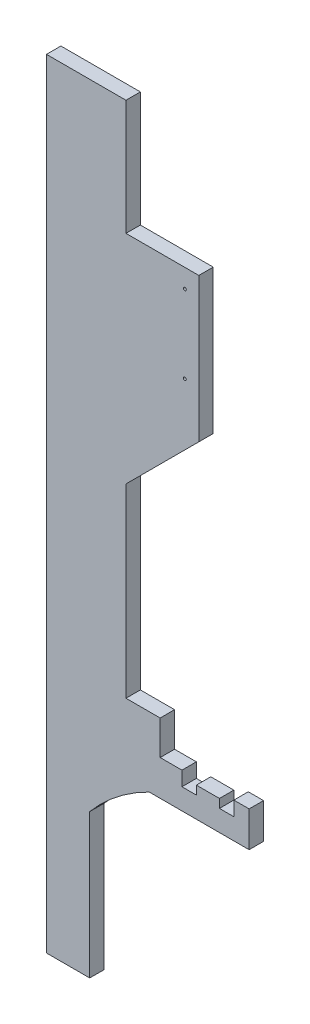
SolidWorks part; units mm, degrees
material "Balsa"
ref_plane "Plan de face" through (0, 0, 0) normal (0, 0, 1) x (1, 0, 0)
ref_plane "Plan de dessus" through (0, 0, 0) normal (0, 1, 0) x (1, 0, 0)
ref_plane "Plan de droite" through (0, 0, 0) normal (1, 0, 0) x (0, 0, -1)
sketch "Esquisse1" plane through (0, 0, 0) normal (0, 0, 1) x (1, 0, 0)
  line L0 (70.2972, 66.1864) -> (70.2972, 78.4512)
  line L1 (0, 270) -> (27.5725, 270)
  line L2 (70.2972, 78.4512) -> (39.4393, 78.4512)
  line L3 (15, 50) -> (15, 0)
  line L4 (0, 270) -> (0, 0)
  line L5 (15, 0) -> (0, 0)
  line L6 (27.5725, 270) -> (27.5725, 230)
  line L7 (35.67, 66.1864) -> (70.2972, 66.1864)
  line L8 (27.5725, 154.7175) -> (52.855, 180)
  line L9 (52.855, 180) -> (52.855, 230)
  line L10 (27.5725, 230) -> (52.855, 230)
  line L11 (27.5725, 154.7175) -> (27.5725, 90.334)
  line L12 (27.5725, 90.334) -> (39.4393, 90.334)
  line L13 (39.4393, 90.334) -> (39.4393, 78.4512)
  arc A0 (15, 50) -> (35.67, 66.1864) centre (63.603, 9.2251) cw
  dimension "D1" = 270
  dimension "D2" = 40
  dimension "D3" = 15
  dimension "D4" = 50
  dimension "D5" = 50
  dimension "D6" = 135
extrude "Boss.-Extru.1" add sketch "Esquisse1" along normal blind 5
sketch "Esquisse3" plane through (0, 0, 5) normal (0, 0, 1) x (1, 0, 0)
  line L0 (70.2972, 78.4512) -> (39.4393, 78.4512) construction
  line L1 (52, 76.4512) -> (60, 76.4512)
  line L2 (47, 78.4512) -> (47, 73.4512)
  line L3 (47, 73.4512) -> (52, 73.4512)
  line L4 (52, 76.4512) -> (52, 73.4512)
  line L5 (47, 78.4512) -> (65, 78.4512)
  line L7 (65, 78.4512) -> (65, 73.4512)
  line L8 (65, 73.4512) -> (60, 73.4512)
  line L9 (60, 76.4512) -> (60, 73.4512)
  line L10 (70.2972, 66.1864) -> (70.2972, 78.4512) construction
  circle A0 centre (48, 223.5) radius 0.5
  circle A1 centre (48, 196.5) radius 0.5
  dimension "D1" = 5
  dimension "D2" = 5
  dimension "D3" = 8
  dimension "D4" = 5
  dimension "D5" = 3
  dimension "D6" = 5.2972
extrude "Enlèv. mat.-Extru.1" cut sketch "Esquisse3" against normal blind 5
